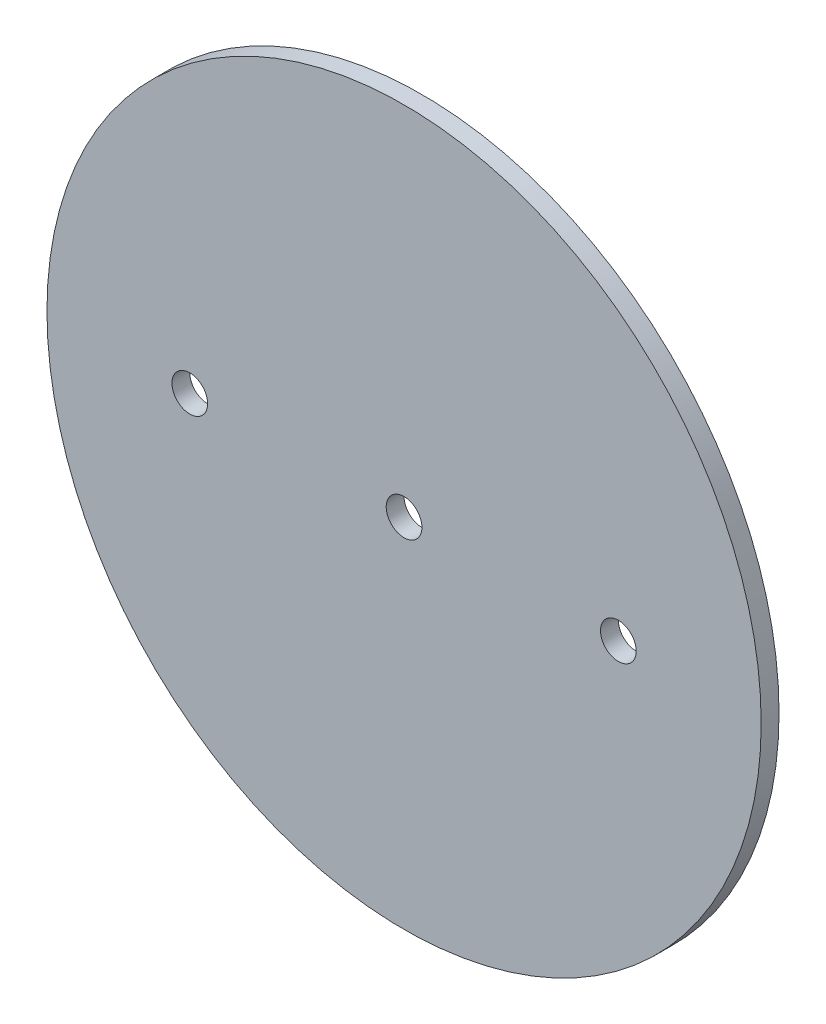
SolidWorks part; units mm, degrees
ref_plane "Front Plane" through (0, 0, 0) normal (0, 0, 1) x (1, 0, 0)
ref_plane "Top Plane" through (0, 0, 0) normal (0, 1, 0) x (1, 0, 0)
ref_plane "Right Plane" through (0, 0, 0) normal (1, 0, 0) x (0, 0, -1)
sketch "Sketch1" plane through (0, 0, 0) normal (0, 0, 1) x (1, 0, 0)
  circle A0 centre (0, 0) radius 63.5
  dimension "D1" = 127
extrude "Boss-Extrude1" add sketch "Sketch1" along normal mid plane 3.175
sketch "Sketch2" plane through (0, 0, 1.5875) normal (0, 0, 1) x (1, 0, 0)
  line L0 (-1000, 0) -> (49000, 0) construction
  point P1 (0, 0)
  point P4 (38.1, 0)
  point P5 (-38.1, 0)
  dimension "D1" = 38.1
  dimension "D2" = 76.2
hole_wizard "1/4 (0.25) Diameter Hole1" positions "Sketch2" profile "Sketch3" hole size "1/4" standard "ANSI Inch" end condition through all
sketch "Sketch3" plane through (-38.1, 0, 1.5875) normal (1, 0, 0) x (0, -1, 0)
  line L0 (0, 0) -> (0, 3.175)
  line L1 (0, 3.175) -> (3.175, 3.175)
  line L2 (3.175, 3.175) -> (3.175, 0)
  line L5 (3.175, 0) -> (0, 0)
  line L11 (0, -6.35) -> (0, 107.95) construction
  dimension "Thru Hole Dia." = 6.35
  dimension "Thru Hole Depth" = 3.175
equation "\"AIRFRAME_OD\"= 5.15in"
equation "\"AIRFRAME_ID\"= 5.00in"
equation "\"FLAT_T\"= 0.125in"
equation "\"NOSE_EXP_L\"= 27in"
equation "\"NOSE_SHOULDER_L\"= 5in"
equation "\"MAIN_L\"= 30in"
equation "\"RECO_COUP_L\"= 10in"
equation "\"RECO_SWITCH_L\"= 2in"
equation "\"DROGUE_L\"= 20in"
equation "\"ATS_FORE_COUP_L\"= 5.5in"
equation "\"ATS_AFT_COUP_L\"= 4.5in"
equation "\"LOWER_L\"= 30in"
equation "\"FIN_N\"= 4"
equation "\"CR_AFT_X\"= 0.5in"
equation "\"CR_FORE_X\"= 9.25in"
equation "\"FIN_ROOT\"= 8in"
equation "\"FIN_X\"= 0.75in"
equation "\"MOTOR_OD\"= 3.091in"
equation "\"MOTOR_ID\"= 3.00in"
equation "\"COUPLER_OD\"= 4.998in"
equation "\"COUPLER_ID\"= 4.88in"
equation "\"D1@Sketch1\"=\"AIRFRAME_ID\""
equation "\"D1@Boss-Extrude1\"=\"FLAT_T\""
equation "\"RECO_ROD_X\"= 3.5in"
equation "\"ATS_ROD_X\"= 3in"
equation "\"D1@Sketch2\"=\"ATS_ROD_X\"*0.5"
equation "\"D2@Sketch2\"=\"ATS_ROD_X\""
equation "\"MOTOR_L\"= 14in"
equation "\"MOTOR_LOWER_X\"= 2in"
